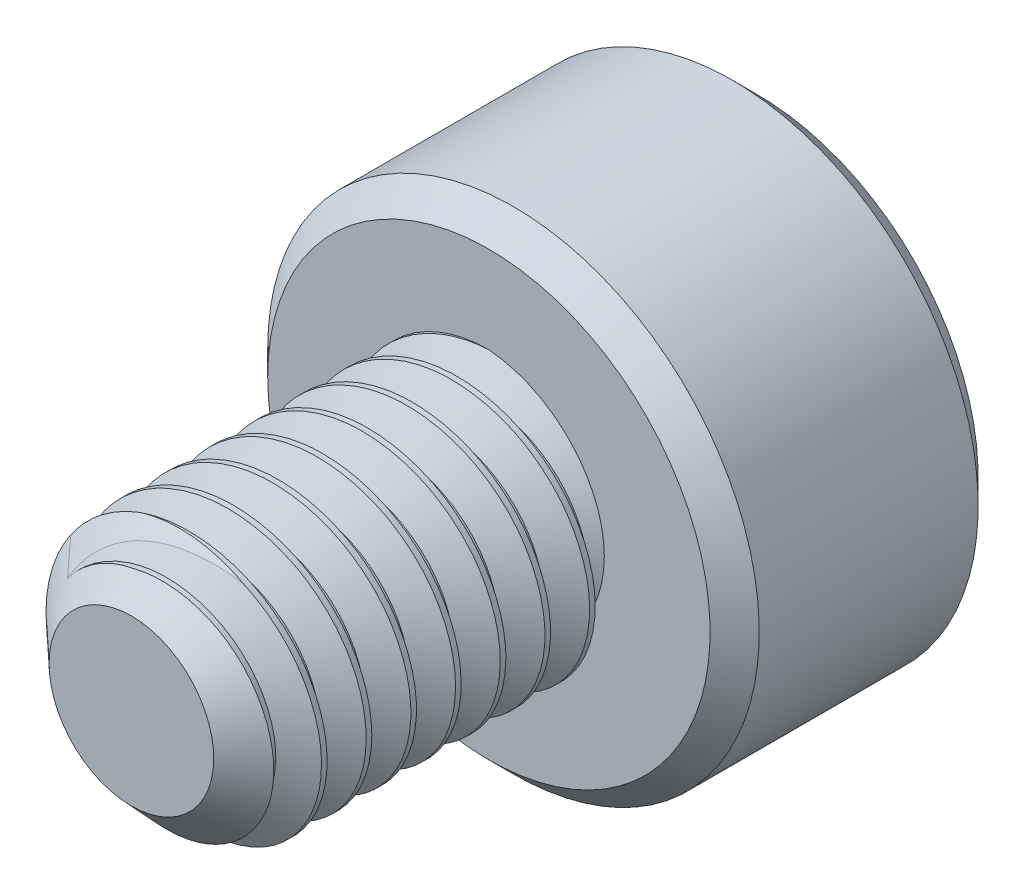
SolidWorks part; units mm, degrees
material "AISI 304"
ref_plane "Front Plane" through (0, 0, 0) normal (0, 0, 1) x (1, 0, 0)
ref_plane "Top Plane" through (0, 0, 0) normal (0, 1, 0) x (1, 0, 0)
ref_plane "Right Plane" through (0, 0, 0) normal (1, 0, 0) x (0, 0, -1)
sketch "Sketch1" plane through (0, 0, 0) normal (0, 0, 1) x (1, 0, 0)
  circle A0 centre (0, 0) radius 1.5
  dimension "OD" = 3
extrude "Extrude1" add sketch "Sketch1" against normal blind 4
sketch "Sketch2" plane through (0, 0, 0) normal (0, 0, 1) x (1, 0, 0)
  circle A0 centre (0, 0) radius 1.5 construction
  circle A1 centre (0, 0) radius 1.5
curve "Helix/Spiral1" pitch 0.5 height 4.5 radius 1.5 centre (0, 0, 0) axis (0, 0, -1) start towards (0, 1, 0) parameters "pitch"=0.5
sketch "Sketch3" plane through (0, 0, 0) normal (1, 0, 0) x (0, 0, -1)
  line L0 (-0.4375, 1.5) -> (-0.25, 1.1752)
  line L1 (-0.25, 1.1752) -> (-0.1875, 1.1752)
  line L2 (-0.1875, 1.1752) -> (0, 1.5)
  line L3 (-0.4375, 1.5) -> (0, 1.5)
  line L4 (-0.2187, 1.5) -> (-0.2187, 1.1752) construction
  line L5 (-0.3438, 1.3376) -> (-0.0937, 1.3376) construction
  line L6 (0, 1.5) -> (0, -1.5) construction
  dimension "D1" = 0.0625
  dimension "D2" = 0.25
  dimension "D3" = 60
sweep "Cut-Sweep1" cut profiles "Sketch3" path "Helix/Spiral1"
sketch "Sketch4" plane through (0, 0, 0) normal (1, 0, 0) x (0, 0, -1)
  line L0 (0.5397, 1.5) -> (0, 0.9212)
  line L1 (0, 0.9212) -> (0, 1.5)
  line L2 (0.5397, 1.5) -> (0, 1.5)
  line L3 (-0.4375, 1.5) -> (0, 1.5) construction
  line L4 (0, 0) -> (7.0209, 0) construction
  dimension "D1" = 47
  dimension "D2" = 0.254
revolve "Cut-Revolve1" cut sketch "Sketch4" angle 360 about L4
sketch "Sketch5" plane through (0, 0, 0) normal (1, 0, 0) x (0, 0, -1)
  line L0 (4, -1.1822) -> (4, 1.0703) construction
  line L1 (4, 1.627) -> (28.1202, 1.627)
  line L2 (4, 1.627) -> (4, 0)
  line L3 (4, 0) -> (28, 0)
  line L4 (28, 1.2968) -> (28, 0)
  line L5 (28.1202, 1.627) -> (28, 1.2968)
  line L6 (0, 0) -> (9.9695, 0) construction
  point P3 (28, 1.627)
  point P10 (28, 1.627)
  dimension "D1" = 0.3302
  dimension "Thread min" = 28
  dimension "D2" = 0.127
  dimension "D3" = 20
revolve "partially thread" [suppressed] add sketch "Sketch5" angle 360 about L6
sketch "Sketch6" plane through (0, 0, -4) normal (0, 0, -1) x (-1, 0, 0)
  circle A0 centre (0, 0) radius 2.75
  dimension "head dia" = 5.5
extrude "Extrude2" add sketch "Sketch6" along normal blind 3
sketch "Sketch7" plane through (0, 0, -7) normal (0, 0, -1) x (-1, 0, 0)
  line L1 (0, 1.4434) -> (-1.25, 0.7217)
  line L2 (-1.25, 0.7217) -> (-1.25, -0.7217)
  line L3 (-1.25, -0.7217) -> (0, -1.4434)
  line L4 (0, -1.4434) -> (1.25, -0.7217)
  line L5 (1.25, -0.7217) -> (1.25, 0.7217)
  line L6 (1.25, 0.7217) -> (0, 1.4434)
  circle A0 centre (0, 0) radius 1.25 construction
  dimension "hex dia" = 2.5
extrude "Cut-Extrude1" cut sketch "Sketch7" against normal blind 1.875
sketch "Sketch8" plane through (0, 0, -7) normal (0, 0, -1) x (-1, 0, 0)
  circle A0 centre (0, 0) radius 1.4434
extrude "Cut-Extrude2" cut sketch "Sketch8" against normal through all draft 45
chamfer "Chamfer1" distance 0.275 angle 45 2 edges at (-2.75, 0, -7) (-2.75, 0, -4)
sketch "Sketch9" plane through (0, 0, 0) normal (1, 0, 0) x (0, 0, -1)
  line L0 (0, 1.5) -> (0, -1.5) construction
  line L1 (2.75, 1.5) -> (2.75, -1.5) construction
  dimension "D1" = 2.75
  dimension "D4" = 0.635
  dimension "D5" = 0.3302
equation "\"D3@Helix/Spiral1\" = \"screw length@Extrude1\"+\"pitch@Helix/Spiral1\""
equation "\"D1@Sketch3\" = \"pitch@Helix/Spiral1\"*.125"
equation "\"D2@Sketch3\" = \"pitch@Helix/Spiral1\"*.5"
equation "\"D1@Cut-Extrude1\" = \"hex dia@Sketch7\"*.75"
equation "\"D1@Chamfer1\" = \"head dia@Sketch6\"*.05"
equation "\"D1@Sketch9\" = \"pitch@Helix/Spiral1\"*5.5"
